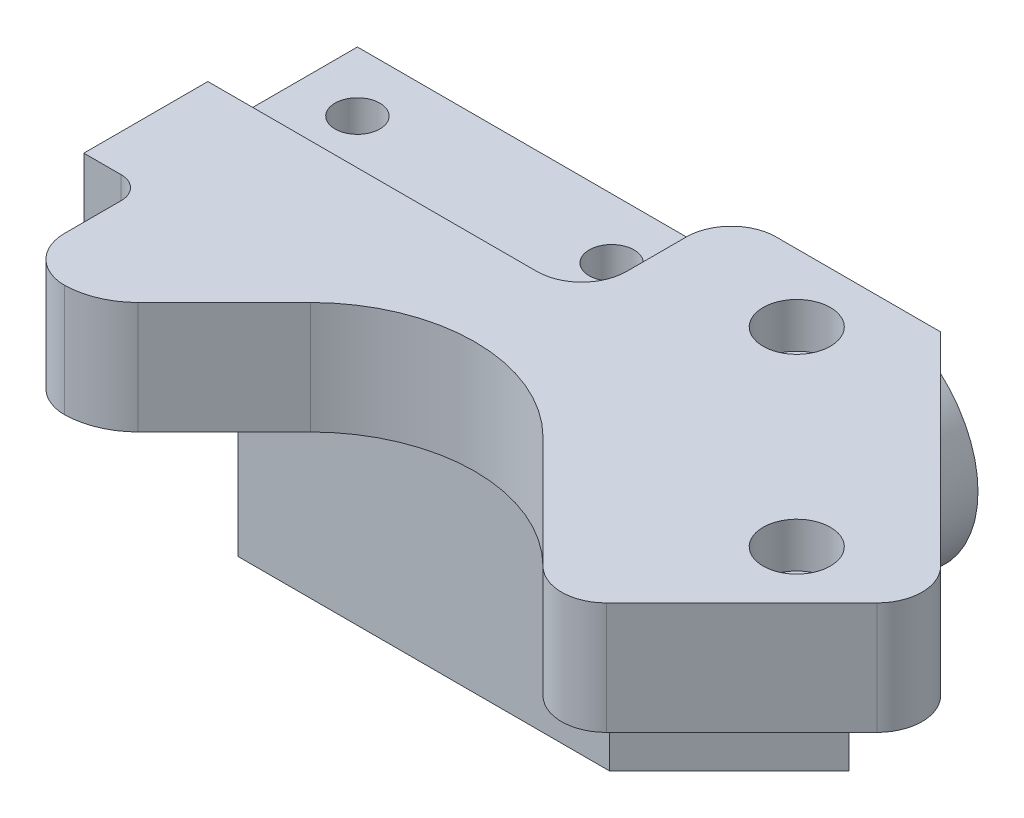
SolidWorks part; units mm, degrees
ref_plane "Front Plane" through (0, 0, 0) normal (0, 0, 1) x (1, 0, 0)
ref_plane "Top Plane" through (0, 0, 0) normal (0, 1, 0) x (1, 0, 0)
ref_plane "Right Plane" through (0, 0, 0) normal (1, 0, 0) x (0, 0, -1)
sketch "Sketch3" plane through (0, 5.4967, 0) normal (0, -1, 0) x (1, 0, 0)
  line L8 (-43.5722, -214.6789) -> (-43.5722, 19.4919) construction
  line L9 (-58.5723, 18.9356) -> (-63.5723, 18.9356)
  line L12 (-35.7941, 11.7137) -> (-26.1725, 21.3353)
  line L13 (-58.5723, 18.9356) -> (-51.3504, 11.7137)
  line L14 (-26.1725, 21.3353) -> (-12.8767, 8.0395)
  line L16 (-28.5722, -7.6561) -> (-12.8767, 8.0395)
  line L17 (-58.5723, -7.6561) -> (-28.5722, -7.6561)
  line L18 (-63.5723, 18.9356) -> (-63.5723, 5.6398)
  line L19 (-43.5722, 19.4919) -> (-32.5722, 19.4919) construction
  line L20 (-58.5723, -7.6561) -> (-63.5723, 5.6398)
  circle A0 centre (-43.5722, 19.4919) radius 11 construction
  arc A2 (-51.3504, 11.7137) -> (-35.7941, 11.7137) centre (-43.5722, 19.4919) ccw
  circle A4 centre (-33.6728, -3.1355) radius 1.5
  circle A5 centre (-20.9448, 9.5924) radius 1.5
extrude "Boss-Extrude1" add sketch "Sketch3" along normal blind 8
sketch "Sketch4" plane through (0, 25.4967, 0) normal (0, 1, 0) x (1, 0, 0)
  line L0 (-67.5734, 21.5545) -> (-67.5734, -11.9295) construction
  line L3 (-65.0723, -10.6398) -> (-67.5734, -10.6398)
  line L4 (-67.5734, 7.6561) -> (-67.5734, -10.6398)
  line L5 (-63.5723, -5.6398) -> (-63.5723, -18.9356)
  line L6 (-63.5723, -12.1398) -> (-63.5723, -18.9356)
  line L10 (-26.1725, -21.3353) -> (-12.8767, -8.0395)
  line L11 (-28.5722, 7.6561) -> (-58.5723, 7.6561)
  line L19 (-28.5722, 7.6561) -> (-67.5734, 7.6561)
  line L21 (-26.1725, -21.3353) -> (-12.8767, -8.0395)
  line L22 (-12.8767, -8.0395) -> (-28.5722, 7.6561)
  line L23 (-12.8767, -8.0395) -> (-28.5722, 7.6561)
  line L26 (-58.5723, 7.6561) -> (-63.5723, -5.6398)
  line L27 (-63.5723, -18.9356) -> (-58.5723, -18.9356)
  line L28 (-63.5723, -18.9356) -> (-58.5723, -18.9356)
  line L29 (-58.5723, -18.9356) -> (-51.3504, -11.7137)
  line L30 (-58.5723, -18.9356) -> (-51.3504, -11.7137)
  line L31 (-35.7941, -11.7137) -> (-26.1725, -21.3353)
  line L32 (-35.7941, -11.7137) -> (-26.1725, -21.3353)
  arc A1 (-35.7941, -11.7137) -> (-51.3504, -11.7137) centre (-43.5722, -19.4919) ccw
  arc A2 (-35.7941, -11.7137) -> (-51.3504, -11.7137) centre (-43.5722, -19.4919) ccw
  arc A3 (-63.5723, -12.1398) -> (-65.0723, -10.6398) centre (-65.0723, -12.1398) ccw
  dimension "D3" = 1.5
  dimension "D1" = 0
extrude "Boss-Extrude2" add sketch "Sketch4" along normal blind 8 separate body
sketch "Sketch9" plane through (0, 25.4967, 0) normal (0, -1, 0) x (1, 0, 0)
  line L0 (-34.7096, -7.6561) -> (-42.7096, 0.3439)
  line L2 (-42.7096, 0.3439) -> (-58.4567, 0.3439)
  line L3 (-34.7096, -7.6561) -> (-58.4567, -7.6561)
  line L4 (-58.4567, -7.6561) -> (-58.4567, 0.3439)
  line L6 (-58.5723, -7.6561) -> (-28.5722, -7.6561) construction
  line L7 (-20.9448, 9.5924) -> (-33.6728, -3.1355) construction
  dimension "D1" = 8
extrude "Boss-Extrude3" add sketch "Sketch9" along normal up to surface (20 mm away) up to face at (-44.3395, 5.4967, 8.6421)
sketch "Sketch10" plane through (0, 0, -7.6561) normal (0, 0, -1) x (-1, 0, 0)
  circle A0 centre (43.5723, 15.4967) radius 5
  circle A1 centre (43.5723, 15.4967) radius 7.5
extrude "Boss-Extrude4" add sketch "Sketch10" along normal blind 10
fillet "Fillet1" radius 3 6 edges at (-26.1725, 29.4967, 21.3353) (-12.8767, 29.4967, 8.0395) (-26.1725, 1.4967, 21.3353) (-12.8767, 1.4967, 8.0395) (-63.5723, 29.4967, 18.9356) (-63.5723, 1.4967, 18.9356)
sketch "Sketch11" plane through (0, 25.4967, 0) normal (0, -1, 0) x (1, 0, 0)
  line L12 (-58.5723, 18.9356) -> (-60.5723, 18.9356)
  line L13 (-63.5723, 15.9356) -> (-63.5723, 12.1398)
  line L15 (-67.5734, -7.6561) -> (-58.4567, -7.6561)
  line L16 (-58.4567, -7.6561) -> (-58.4567, 0.3439)
  line L17 (-58.4567, 0.3439) -> (-42.7096, 0.3439)
  line L18 (-42.7096, 0.3439) -> (-34.7096, -7.6561)
  line L19 (-34.7096, -7.6561) -> (-28.5722, -7.6561)
  line L20 (-28.5722, -7.6561) -> (-14.998, 5.9181)
  line L21 (-14.998, 10.1608) -> (-24.0512, 19.214)
  line L22 (-28.2939, 19.214) -> (-35.7941, 11.7137)
  line L23 (-51.3504, 11.7137) -> (-58.5723, 18.9356)
  line L24 (-58.5723, 18.9356) -> (-60.5723, 18.9356)
  line L25 (-63.5723, 15.9356) -> (-63.5723, 12.1398)
  line L27 (-67.5734, -7.6561) -> (-58.4567, -7.6561)
  line L28 (-58.4567, -7.6561) -> (-58.4567, 0.3439)
  line L29 (-58.4567, 0.3439) -> (-42.7096, 0.3439)
  line L30 (-42.7096, 0.3439) -> (-34.7096, -7.6561)
  line L31 (-34.7096, -7.6561) -> (-28.5722, -7.6561)
  line L32 (-28.5722, -7.6561) -> (-14.998, 5.9181)
  line L33 (-14.998, 10.1608) -> (-24.0512, 19.214)
  line L34 (-28.2939, 19.214) -> (-35.7941, 11.7137)
  line L35 (-51.3504, 11.7137) -> (-58.5723, 18.9356)
  line L39 (-65.0723, 10.6398) -> (-67.5734, 10.6398)
  line L40 (-65.0723, 10.6398) -> (-67.5734, 10.6398)
  line L41 (-67.5734, 10.6398) -> (-67.5734, -7.6561)
  line L42 (-67.5734, 10.6398) -> (-67.5734, -7.6561)
  arc A4 (-60.5723, 18.9356) -> (-63.5723, 15.9356) centre (-60.5723, 15.9356) ccw
  arc A5 (-14.998, 5.9181) -> (-14.998, 10.1608) centre (-17.1193, 8.0395) ccw
  arc A6 (-24.0512, 19.214) -> (-28.2939, 19.214) centre (-26.1725, 17.0926) ccw
  arc A7 (-51.3504, 11.7137) -> (-35.7941, 11.7137) centre (-43.5722, 19.4919) ccw
  arc A8 (-60.5723, 18.9356) -> (-63.5723, 15.9356) centre (-60.5723, 15.9356) ccw
  arc A9 (-14.998, 5.9181) -> (-14.998, 10.1608) centre (-17.1193, 8.0395) ccw
  arc A10 (-24.0512, 19.214) -> (-28.2939, 19.214) centre (-26.1725, 17.0926) ccw
  arc A11 (-51.3504, 11.7137) -> (-35.7941, 11.7137) centre (-43.5722, 19.4919) ccw
  arc A14 (-65.0723, 10.6398) -> (-63.5723, 12.1398) centre (-65.0723, 12.1398) ccw
  arc A15 (-65.0723, 10.6398) -> (-63.5723, 12.1398) centre (-65.0723, 12.1398) ccw
  dimension "D1" = 0
extrude "Cut-Extrude1" cut sketch "Sketch11" against normal blind 0.5
sketch "Sketch12" plane through (0, 5.4967, 0) normal (0, 1, 0) x (1, 0, 0)
  line L0 (-67.5734, -10.6398) -> (-65.0723, -10.6398) construction
  line L1 (-67.5734, 7.6561) -> (-67.5734, -10.6398) construction
  line L3 (-67.5734, -10.6398) -> (-65.0723, -10.6398)
  line L4 (-67.5734, 7.6561) -> (-67.5734, -10.6398)
  line L5 (-65.6492, -5.6398) -> (-67.5734, 7.6561)
  line L12 (-63.5723, -5.6398) -> (-63.5723, -15.9356)
  line L13 (-60.5723, -18.9356) -> (-58.5723, -18.9356)
  line L14 (-58.5723, -18.9356) -> (-51.3504, -11.7137)
  line L15 (-35.7941, -11.7137) -> (-28.2939, -19.214)
  line L16 (-24.0512, -19.214) -> (-14.998, -10.1608)
  line L17 (-14.998, -5.9181) -> (-28.5722, 7.6561)
  line L18 (-28.5722, 7.6561) -> (-34.7096, 7.6561)
  line L19 (-34.7096, 7.6561) -> (-42.7096, -0.3439)
  line L20 (-42.7096, -0.3439) -> (-58.4567, -0.3439)
  line L21 (-58.4567, -0.3439) -> (-58.4567, 7.6561)
  line L22 (-58.4567, 7.6561) -> (-58.5723, 7.6561)
  line L23 (-58.5723, 7.6561) -> (-63.5723, -5.6398)
  line L24 (-63.5723, -12.1398) -> (-63.5723, -15.9356)
  line L25 (-60.5723, -18.9356) -> (-58.5723, -18.9356)
  line L26 (-58.5723, -18.9356) -> (-51.3504, -11.7137)
  line L27 (-35.7941, -11.7137) -> (-28.2939, -19.214)
  line L28 (-24.0512, -19.214) -> (-14.998, -10.1608)
  line L29 (-14.998, -5.9181) -> (-28.5722, 7.6561)
  line L30 (-28.5722, 7.6561) -> (-34.7096, 7.6561)
  line L31 (-34.7096, 7.6561) -> (-42.7096, -0.3439)
  line L32 (-42.7096, -0.3439) -> (-58.4567, -0.3439)
  line L33 (-58.4567, -0.3439) -> (-58.4567, 7.6561)
  line L34 (-58.4567, 7.6561) -> (-58.5723, 7.6561)
  line L35 (-58.5723, 7.6561) -> (-62.8412, -3.6957)
  arc A0 (-65.6492, -5.6398) -> (-62.8412, -3.6957) centre (-65.6492, -2.6398) ccw
  arc A1 (-65.0723, -10.6398) -> (-63.5723, -12.1398) centre (-65.0723, -12.1398) cw
  arc A4 (-63.5723, -15.9356) -> (-60.5723, -18.9356) centre (-60.5723, -15.9356) ccw
  arc A5 (-35.7941, -11.7137) -> (-51.3504, -11.7137) centre (-43.5722, -19.4919) ccw
  arc A6 (-28.2939, -19.214) -> (-24.0512, -19.214) centre (-26.1725, -17.0926) ccw
  arc A7 (-14.998, -10.1608) -> (-14.998, -5.9181) centre (-17.1193, -8.0395) ccw
  arc A8 (-63.5723, -15.9356) -> (-60.5723, -18.9356) centre (-60.5723, -15.9356) ccw
  arc A9 (-35.7941, -11.7137) -> (-51.3504, -11.7137) centre (-43.5722, -19.4919) ccw
  arc A10 (-28.2939, -19.214) -> (-24.0512, -19.214) centre (-26.1725, -17.0926) ccw
  arc A11 (-14.998, -10.1608) -> (-14.998, -5.9181) centre (-17.1193, -8.0395) ccw
  dimension "D1" = 0
extrude "Cut-Extrude2" cut sketch "Sketch12" against normal blind 0.5
chamfer "Chamfer1" distance 3 angle 45 1 edges at (-36.0723, 15.4967, -7.6561)
sketch "Sketch13" plane through (0, 25.9967, 0) normal (0, -1, 0) x (1, 0, 0)
  line L0 (-58.4567, -7.6561) -> (-58.4567, 0.3439) construction
  line L2 (-58.4567, -7.6561) -> (-58.4567, 0.3439)
  line L3 (-67.5734, 0.3439) -> (-67.5734, -7.6561)
  line L4 (-58.4567, 0.3439) -> (-67.5734, 0.3439)
  line L5 (-67.5734, -7.6561) -> (-58.4567, -7.6561) construction
  line L6 (-67.5734, -7.6561) -> (-58.4567, -7.6561)
  line L7 (-67.5734, -21.5548) -> (-67.5734, 11.9292) construction
extrude "Boss-Extrude5" add sketch "Sketch13" along normal up to surface (21 mm away) up to face at (-22.4448, 4.9967, 9.5924)
fillet "Fillet2" radius 15 1 edges at (-63.5723, 1.2467, 5.6398)
fillet "Fillet3" radius 5 2 edges at (-58.5723, 29.7467, 18.9356) (-58.5723, 1.2467, 18.9356)
sketch "Sketch14" plane through (0, -2.5033, 0) normal (0, -1, 0) x (1, 0, 0)
  line L10 (-62.6123, 3.0871) -> (-58.5723, -7.6561) construction
  line L11 (-63.5723, 15.9356) -> (-63.5723, 8.367) construction
  line L12 (-62.6123, 3.0871) -> (-58.5723, -7.6561)
  line L13 (-63.5723, 12.1398) -> (-63.5723, 8.367)
  line L19 (-67.5734, -7.6561) -> (-28.5722, -7.6561)
  line L20 (-28.5722, -7.6561) -> (-12.8767, 8.0395)
  line L21 (-12.8767, 8.0395) -> (-26.1725, 21.3353)
  line L22 (-26.1725, 21.3353) -> (-35.7941, 11.7137)
  line L23 (-51.3504, 11.7137) -> (-58.5723, 18.9356)
  line L24 (-58.5723, 18.9356) -> (-63.5723, 18.9356)
  line L25 (-63.5723, 18.9356) -> (-63.5723, 12.1398)
  line L26 (-65.0723, 10.6398) -> (-67.5734, 10.6398)
  line L27 (-67.5734, 10.6398) -> (-67.5734, -7.6561)
  line L28 (-67.5734, -7.6561) -> (-58.5723, -7.6561)
  line L35 (-65.0723, 10.6398) -> (-67.5734, 10.6398)
  line L36 (-67.5734, 10.6398) -> (-67.5734, -7.6561)
  arc A6 (-63.5723, 8.367) -> (-62.6123, 3.0871) centre (-48.5723, 8.367) ccw construction
  arc A7 (-63.5723, 8.367) -> (-62.6123, 3.0871) centre (-48.5723, 8.367) ccw
  arc A8 (-51.3504, 11.7137) -> (-35.7941, 11.7137) centre (-43.5722, 19.4919) ccw
  arc A9 (-65.0723, 10.6398) -> (-63.5723, 12.1398) centre (-65.0723, 12.1398) ccw
  arc A11 (-65.0723, 10.6398) -> (-63.5723, 12.1398) centre (-65.0723, 12.1398) ccw
  dimension "D1" = 0
extrude "Boss-Extrude6" add sketch "Sketch14" against normal up to surface (7.5 mm away) up to face at (-22.4448, 4.9967, 9.5924)
sketch "Sketch15" plane through (0, -2.5033, 0) normal (0, -1, 0) x (1, 0, 0)
  line L0 (-67.5734, -7.6561) -> (-28.5722, -7.6561) construction
  line L1 (-67.5734, 2.3439) -> (-42.5734, 2.3439)
  line L2 (-67.5734, 2.3439) -> (-67.5734, -7.6561)
  line L3 (-67.5734, -7.6561) -> (-42.5734, -7.6561)
  line L4 (-42.5734, 2.3439) -> (-42.5734, -7.6561)
extrude "Cut-Extrude3" cut sketch "Sketch15" against normal blind 3
sketch "Sketch17" plane through (0, 33.4967, 0) normal (0, 1, 0) x (1, 0, 0)
  line L4 (-67.5734, 7.6561) -> (-67.5734, -2.3439)
  line L5 (-42.5734, 7.6561) -> (-67.5734, 7.6561)
  line L6 (-42.5734, -2.3439) -> (-42.5734, 7.6561)
  line L7 (-67.5734, -2.3439) -> (-42.5734, -2.3439)
  line L8 (-67.5734, 7.6561) -> (-67.5734, -2.3439)
  line L9 (-42.5734, 7.6561) -> (-67.5734, 7.6561)
  line L10 (-42.5734, -2.3439) -> (-42.5734, 7.6561)
  line L11 (-67.5734, -2.3439) -> (-42.5734, -2.3439)
  dimension "D1" = 0
extrude "Cut-Extrude4" cut sketch "Sketch17" against normal blind 3
fillet "Fillet4" radius 3 4 edges at (-42.5734, 31.9967, 2.3439) (-42.5734, 31.9967, -7.6561) (-42.5734, -1.0033, 2.3439) (-42.5734, -1.0033, -7.6561)
sketch "Sketch18" plane through (0, -2.5033, 0) normal (0, -1, 0) x (1, 0, 0)
  circle A0 centre (-46.5734, -3.6561) radius 1.5
  circle A1 centre (-63.5734, -3.6561) radius 1.5
extrude "Cut-Extrude5" cut sketch "Sketch18" against normal up to surface (36 mm away) up to face at (-45.1492, 33.4967, 8.1147)
sketch "Sketch20" plane through (0, -2.5033, 0) normal (0, -1, 0) x (1, 0, 0)
  line L1 (-12.2781, 24.9771) -> (-73.2595, 24.9771)
  line L2 (-12.2781, 24.9771) -> (-12.2781, -21.2101)
  line L3 (-12.2781, -21.2101) -> (-73.2595, -21.2101)
  line L4 (-73.2595, 24.9771) -> (-73.2595, -21.2101)
extrude "Cut-Extrude6" cut sketch "Sketch20" against normal up to surface (7.5 mm away) up to face at (-44.9881, 4.9967, 9.2111)
sketch "Sketch21" plane through (0, 25.9967, 0) normal (0, -1, 0) x (1, 0, 0)
  circle A0 centre (-20.9448, 9.5924) radius 1.5
  circle A1 centre (-33.6728, -3.1355) radius 1.5
extrude "Cut-Extrude7" cut sketch "Sketch21" against normal up to surface (7.5 mm away) up to face at (-45.1492, 33.4967, 8.1147)
sketch "Sketch22" plane through (0, 33.4967, 0) normal (0, 1, 0) x (1, 0, 0)
  circle A0 centre (-20.9448, -9.5924) radius 2.25
  circle A1 centre (-33.6728, 3.1355) radius 2.25
extrude "Cut-Extrude8" cut sketch "Sketch22" against normal blind 3
